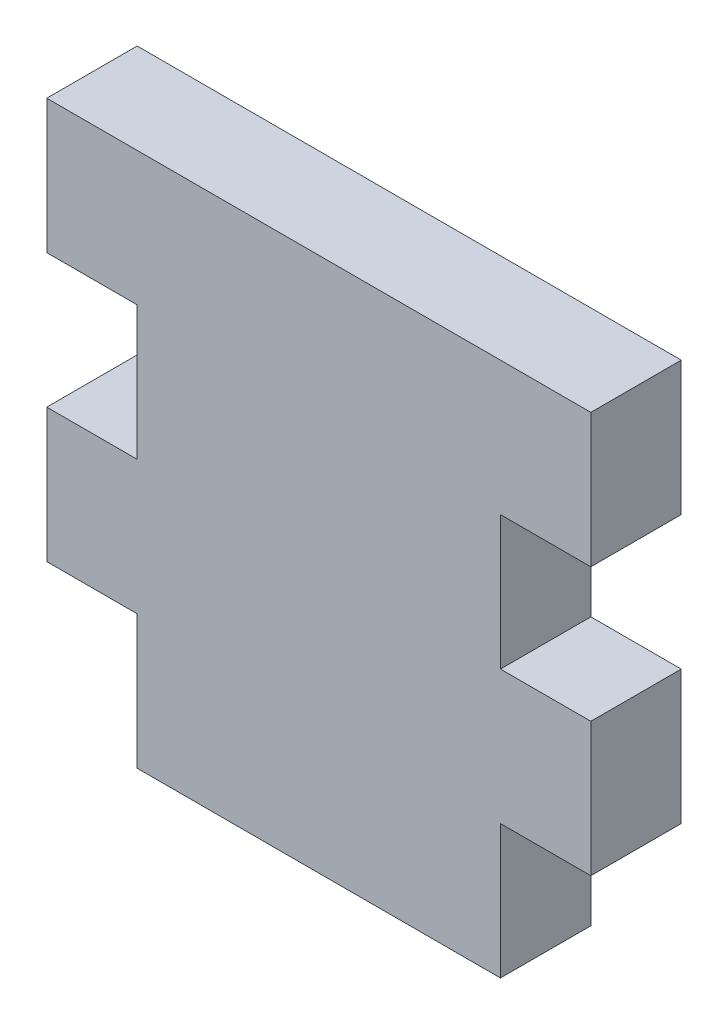
SolidWorks part; units mm, degrees
ref_plane "Front Plane" through (0, 0, 0) normal (0, 0, 1) x (1, 0, 0)
ref_plane "Top Plane" through (0, 0, 0) normal (0, 1, 0) x (1, 0, 0)
ref_plane "Right Plane" through (0, 0, 0) normal (1, 0, 0) x (0, 0, -1)
sketch "Sketch1" plane through (0, 0, 0) normal (0, 0, 1) x (1, 0, 0)
  line L1 (-88.0852, 14.1109) -> (-39.0124, 14.1109)
  line L2 (-88.0852, 14.1109) -> (-88.0852, -34.1491)
  line L3 (-88.0852, -34.1491) -> (-39.0124, -34.1491)
  line L4 (-39.0124, 14.1109) -> (-39.0124, -34.1491)
  dimension "D1" = 48.26
  dimension "D2" = 49.0728
extrude "Boss-Extrude1" add sketch "Sketch1" along normal blind 8.1534
sketch "Sketch2" plane through (0, 0, 8.1534) normal (0, 0, 1) x (1, 0, 0)
  line L0 (-88.0852, 14.1109) -> (-88.0852, -34.1491) construction
  line L1 (-88.0852, -34.1491) -> (-79.9318, -34.1491)
  line L2 (-88.0852, -34.1491) -> (-88.0852, -22.0841)
  line L3 (-88.0852, -22.0841) -> (-79.9318, -22.0841)
  line L4 (-79.9318, -34.1491) -> (-79.9318, -22.0841)
  line L5 (-88.0852, -10.0191) -> (-79.9318, -10.0191)
  line L6 (-88.0852, -10.0191) -> (-88.0852, 2.0459)
  line L7 (-88.0852, 2.0459) -> (-79.9318, 2.0459)
  line L8 (-79.9318, -10.0191) -> (-79.9318, 2.0459)
  line L9 (-79.9318, 2.0459) -> (-79.9318, 14.1109) construction
  line L10 (-39.0124, 14.1109) -> (-88.0852, 14.1109) construction
  line L11 (-79.9318, -10.0191) -> (-79.9318, -22.0841) construction
  line L12 (-63.5488, 14.1109) -> (-63.5488, -34.1491) construction
  line L13 (-88.0852, -34.1491) -> (-39.0124, -34.1491) construction
  line L14 (-47.1658, -10.0191) -> (-47.1658, -22.0841) construction
  line L15 (-47.1658, 2.0459) -> (-47.1658, 14.1109) construction
  line L16 (-47.1658, -10.0191) -> (-47.1658, 2.0459)
  line L17 (-39.0124, 2.0459) -> (-47.1658, 2.0459)
  line L18 (-39.0124, -10.0191) -> (-39.0124, 2.0459)
  line L19 (-39.0124, -10.0191) -> (-47.1658, -10.0191)
  line L20 (-47.1658, -34.1491) -> (-47.1658, -22.0841)
  line L21 (-39.0124, -22.0841) -> (-47.1658, -22.0841)
  line L22 (-39.0124, -34.1491) -> (-39.0124, -22.0841)
  line L23 (-39.0124, -34.1491) -> (-47.1658, -34.1491)
  dimension "D1" = 8.1534
extrude "Cut-Extrude1" cut sketch "Sketch2" against normal through all
equation "\"MDF\"= .321in"
equation "\"Foamcore\"= .13in"
equation "\"Gmaterial\"= \"MDF\""
equation "\"D1@Boss-Extrude1\"=\"MDF\""
equation "\"D1@Sketch2\"=\"MDF\""
equation "\"D2@Sketch1\"=\"MDF\"+\"MDF\"+1.29"
